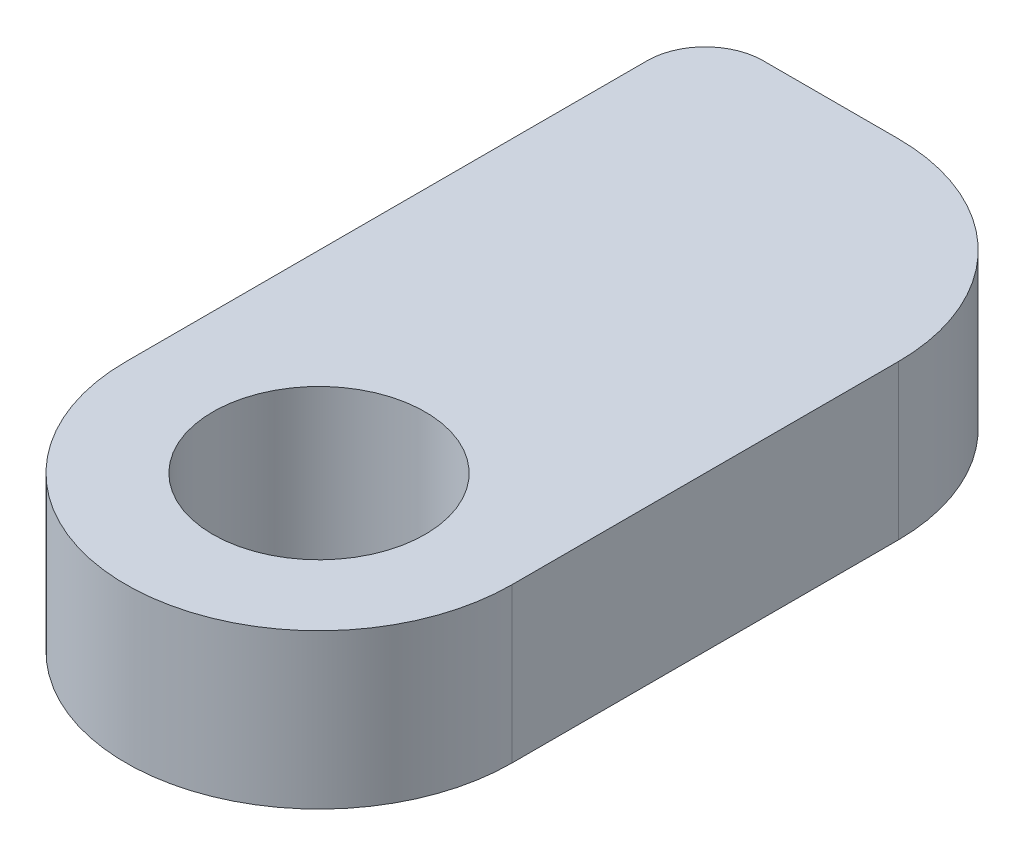
SolidWorks part; units mm, degrees
ref_plane "Front" through (0, 0, 0) normal (0, 0, 1) x (1, 0, 0)
ref_plane "Top" through (0, 0, 0) normal (0, 1, 0) x (1, 0, 0)
ref_plane "Right" through (0, 0, 0) normal (1, 0, 0) x (0, 0, -1)
sketch "Sketch1" plane through (0, 0, 0) normal (0, 1, 0) x (1, 0, 0)
  line L1 (10, 20) -> (-10, 20)
  line L2 (10, 20) -> (10, -20)
  line L3 (10, -20) -> (-10, -20)
  line L4 (-10, 20) -> (-10, -20)
  line L5 (10, 20) -> (-10, -20) construction
  line L6 (10, -20) -> (-10, 20) construction
  circle A0 centre (0, -10) radius 5.5
  point P0 (0, 0)
  dimension "D2" = 11
  dimension "D1" = 20
  dimension "D3" = 40
  dimension "D4" = 10
extrude "Boss-Extrude1" add sketch "Sketch1" along normal blind 8
fillet "Fillet1" 2 edges at (10, 4, 20) (-10, 4, 20) type full round first side face at (10, 4, 0) second side face at (-10, 4, 0) middle face at (0, 4, 20)
fillet "Fillet2" radius 10 1 edges at (10, 4, -20)
fillet "Fillet3" radius 3 1 edges at (-10, 4, -20)
ref_axis "Axis1" through (0, 8, 10) along (0, -1, 0)
